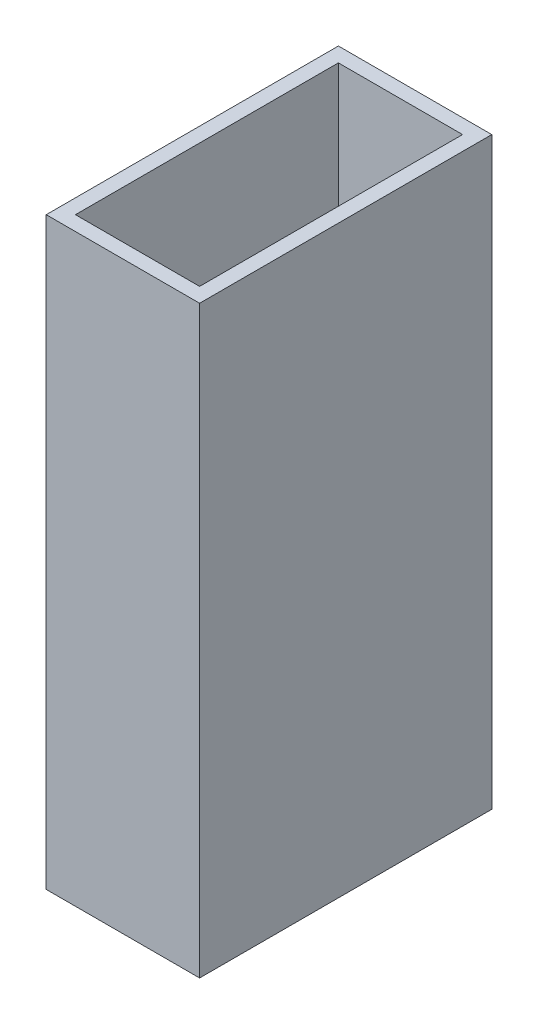
SolidWorks part; units mm, degrees
ref_plane "Front Plane" through (0, 0, 0) normal (0, 0, 1) x (1, 0, 0)
ref_plane "Top Plane" through (0, 0, 0) normal (0, 1, 0) x (1, 0, 0)
ref_plane "Right Plane" through (0, 0, 0) normal (1, 0, 0) x (0, 0, -1)
sketch "Sketch1" plane through (0, 0, 0) normal (0, 1, 0) x (1, 0, 0)
  line L0 (0, 58.5294) -> (0, -74.8529) construction
  line L1 (-26.25, 50) -> (26.25, 50)
  line L2 (-26.25, 50) -> (-26.25, -50)
  line L3 (-26.25, -50) -> (26.25, -50)
  line L4 (26.25, 50) -> (26.25, -50)
  line L5 (-67.7941, 0) -> (76.9118, 0) construction
  dimension "D1" = 100
  dimension "D2" = 52.5
extrude "Boss-Extrude1" add sketch "Sketch1" along normal blind 200
shell "Shell1" thickness 5 removed face at (0, 200, 0)
